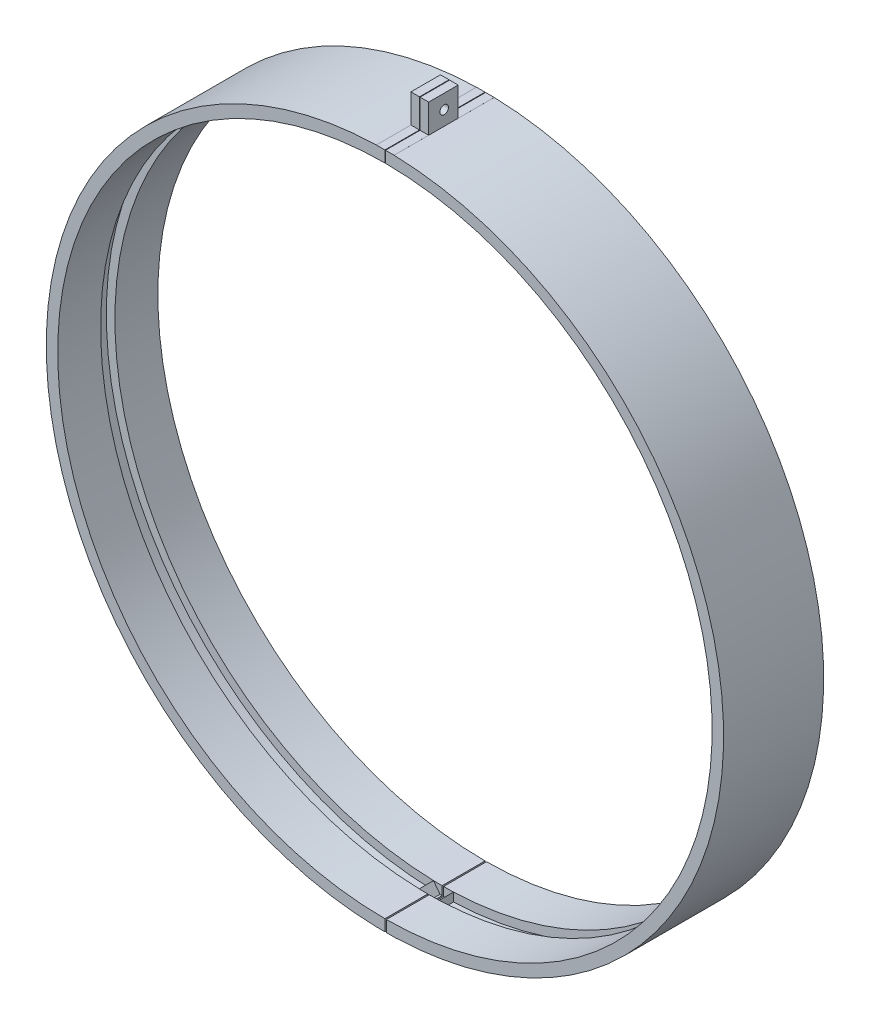
SolidWorks part; units mm, degrees
ref_plane "Front Plane" through (0, 0, 0) normal (0, 0, 1) x (1, 0, 0)
ref_plane "Top Plane" through (0, 0, 0) normal (0, 1, 0) x (1, 0, 0)
ref_plane "Right Plane" through (0, 0, 0) normal (1, 0, 0) x (0, 0, -1)
sketch "Sketch1" plane through (0, 0, 0) normal (0, 0, 1) x (1, 0, 0)
  circle A0 centre (0, 0) radius 114.4
  circle A1 centre (0, 0) radius 118.4
  point P4 (-595.6042, 16.5436)
extrude "Extrude1" add sketch "Sketch1" along normal blind 15
sketch "Sketch2" plane through (0, 0, 15) normal (0, 0, 1) x (1, 0, 0)
  circle A0 centre (0, 0) radius 118.4
  circle A1 centre (0, 0) radius 117.4
  point P0 (0, 0)
extrude "Extrude2" add sketch "Sketch2" along normal blind 5
sketch "Sketch3" plane through (0, 0, 20) normal (0, 0, 1) x (1, 0, 0)
  circle A0 centre (0, 0) radius 118.4
  circle A1 centre (0, 0) radius 114.4
  point P0 (0, 0)
extrude "Extrude3" add sketch "Sketch3" along normal blind 15
sketch "Sketch4" plane through (0, 0, 35) normal (0, 0, 1) x (1, 0, 0)
  line L0 (0, 0) -> (0, 118.4) construction
  line L1 (0, 0) -> (0, -118.4) construction
  line L2 (0, 118.4) -> (0, 128.4)
  line L3 (0, 128.4) -> (-3, 128.4)
  line L4 (-3, 128.4) -> (-3, 114.3607)
  line L5 (0, 128.4) -> (12.1071, 128.4) construction
  line L6 (0.2, 128.4) -> (0.2, 226.0706) construction
  line L7 (0.2, 128.4) -> (3.2, 128.4)
  line L8 (3.2, 128.4) -> (3.2, 114.3552)
  line L9 (3.2, 114.3552) -> (0.2, 118.3998)
  line L10 (0.2, 118.3998) -> (0.2, 128.4)
  line L11 (0, -118.4) -> (0, -260.7808) construction
  line L12 (0, -128.4) -> (-29.7007, -128.4) construction
  line L13 (0, -128.4) -> (32.692, -128.4) construction
  line L14 (0, -118.4) -> (0, -128.4)
  line L15 (0, -128.4) -> (-3, -128.4)
  line L16 (-3, -128.4) -> (-3, -114.3607)
  line L17 (-3, -114.3607) -> (0, -118.4)
  line L18 (0.5, -128.4) -> (0.5, -106.2676) construction
  line L19 (0.5, -118.3989) -> (0.5, -128.4)
  line L20 (0.5, -128.4) -> (4, -128.4)
  line L21 (4, -128.4) -> (4, -114.33)
  line L22 (4, -114.33) -> (0.5, -118.3989)
  circle A0 centre (0, 0) radius 114.4 construction
  circle A1 centre (0, 0) radius 114.4 construction
  circle A2 centre (0, 0) radius 118.4 construction
  arc A3 (-3, 114.3607) -> (0, 118.4) centre (1.2194, 114.3607) cw
  point P0 (109.4647, 33.239)
  point P1 (0, 0)
  point P8 (0, 114.4)
  point P15 (0.2, 128.4)
  point P19 (0.2, 118.3998)
  point P20 (3.2, 128.4)
  point P21 (0, -114.4)
  point P25 (0, -128.4)
  point P29 (-3, -128.4)
  point P31 (0.5, -128.4)
  point P32 (4, -128.4)
  point P37 (0.5, -118.3989)
  dimension "D1" = 10
  dimension "D2" = 3
  dimension "D3" = 0.2
  dimension "D4" = 3
  dimension "D5" = 10
extrude "Extrude4" add sketch "Sketch4" against normal blind 35
sketch "Sketch5" plane through (0, 0, 35) normal (0, 0, 1) x (1, 0, 0)
  line L0 (0, 0) -> (0, 128.4) construction
  line L1 (0, 128.4) -> (0.2, 128.4)
  line L3 (0.2, 128.4) -> (0.2, 110.7631)
  line L4 (0, 128.4) -> (0, 110.7631)
  line L5 (0, 110.7631) -> (0.2, 110.7631)
  line L6 (0, 0) -> (0, -128.4) construction
  line L7 (0, -128.4) -> (0.5, -128.4)
  line L8 (0.5, -128.4) -> (0.5, -107.1151)
  line L9 (0, -128.4) -> (0, -107.1151)
  line L10 (0, -107.1151) -> (0.5, -107.1151)
  point P0 (0, 0)
extrude "Extrude5" cut sketch "Sketch5" against normal through all
sketch "Sketch6" plane through (-3, 0, 0) normal (-1, 0, 0) x (0, 0, 1)
  line L0 (0, 128.4) -> (35, 128.4) construction
  line L1 (35, 128.4) -> (35, 118.362) construction
  line L2 (0, 128.4) -> (0, 118.362) construction
  line L3 (17.5, 118.362) -> (17.5, 128.4) construction
  line L4 (35, 118.362) -> (0, 118.362) construction
  line L5 (0, 123.381) -> (35, 123.381) construction
  line L6 (22.9144, 128.4) -> (35, 128.4)
  line L7 (35, 128.4) -> (35, 118.362)
  line L8 (35, 118.362) -> (22.9144, 118.362)
  line L9 (22.9144, 118.362) -> (22.9144, 128.4)
  line L10 (12.5824, 128.4) -> (12.5824, 118.362)
  line L11 (12.5824, 118.362) -> (0, 118.362)
  line L12 (0, 118.362) -> (0, 128.4)
  line L13 (0, 128.4) -> (12.5824, 128.4)
  line L15 (35, -118.362) -> (35, -128.4) construction
  line L16 (0, -118.362) -> (0, -128.4) construction
  line L17 (0, -128.4) -> (35, -128.4) construction
  line L18 (0, -118.362) -> (35, -118.362) construction
  line L19 (22.9144, -118.362) -> (35, -118.362)
  line L20 (35, -118.362) -> (35, -128.4)
  line L21 (35, -128.4) -> (22.9144, -128.4)
  line L22 (22.9144, -128.4) -> (22.9144, -118.362)
  line L23 (12.5824, -118.362) -> (12.5824, -128.4)
  line L24 (12.5824, -128.4) -> (0, -128.4)
  line L25 (0, -128.4) -> (0, -118.362)
  line L26 (0, -118.362) -> (12.5824, -118.362)
  circle A0 centre (17.5, 123.381) radius 1.5
  circle A1 centre (17.5, -123.381) radius 1.5
  point P0 (17.5, 128.4)
  point P1 (17.5, 236.7334)
  point P4 (35, 123.381)
  point P5 (0, 123.381)
  point P16 (17.5, 123.381)
  point P17 (17.5, -123.381)
  point P22 (12.5824, 128.4)
  point P23 (35, 118.362)
  point P24 (35, 128.4)
  point P25 (0, 118.362)
  point P26 (0, 128.4)
  point P28 (12.5824, 118.362)
  point P30 (22.9144, 128.4)
  point P31 (22.9144, 118.362)
  point P36 (35, -123.381)
  point P39 (0, -123.381)
  point P42 (17.5, -128.4)
  point P45 (17.5, -118.362)
  point P53 (22.9144, -128.4)
  point P54 (12.5824, -128.4)
  point P55 (22.9144, -118.362)
  point P56 (12.5824, -118.362)
  point P57 (35, -118.362)
  point P58 (35, -128.4)
  point P60 (0, -118.362)
  point P62 (0, -128.4)
extrude "Extrude6" cut sketch "Sketch6" against normal through all
